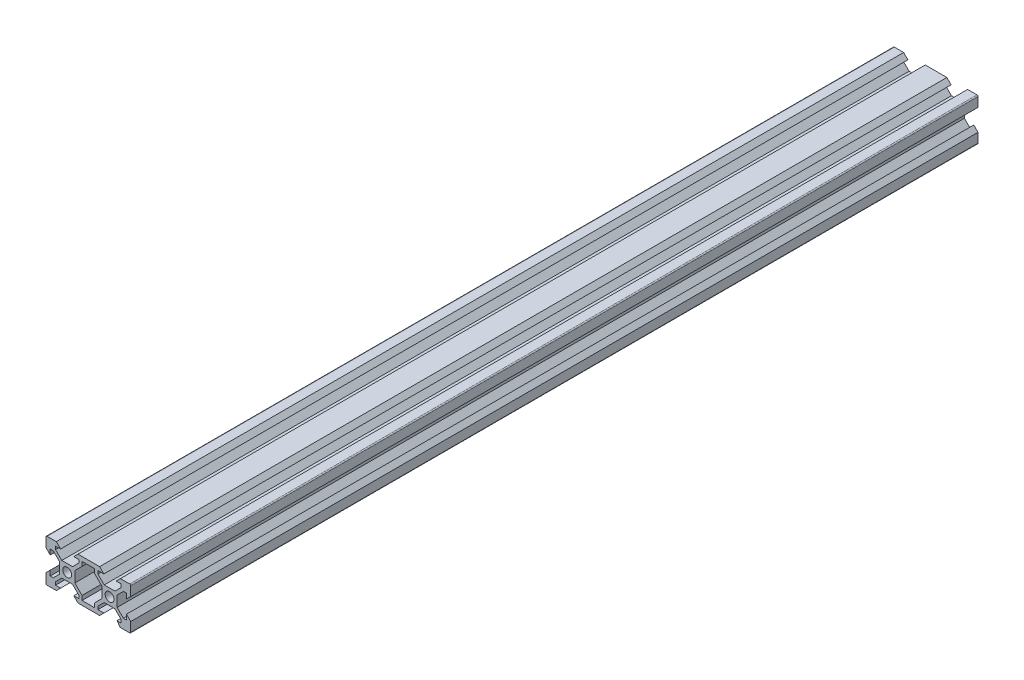
SolidWorks part; units mm, degrees
material "6063-T5"
ref_plane "Front Plane" through (0, 0, 0) normal (0, 0, 1) x (1, 0, 0)
ref_plane "Top Plane" through (0, 0, 0) normal (0, 1, 0) x (1, 0, 0)
ref_plane "Right Plane" through (0, 0, 0) normal (1, 0, 0) x (0, 0, -1)
sketch "Sketch1" plane through (0, 0, 0) normal (0, 0, 1) x (1, 0, 0)
  line L0 (-26.1395, 0) -> (11.0607, 0) construction
  line L1 (0, -20.0817) -> (0, 17.1243) construction
  line L2 (-20, 10.7318) -> (-20, -11.6858) construction
  line L3 (20, 11.8444) -> (20, -11.2237) construction
  line L4 (-23.1467, 10) -> (24.2381, 10) construction
  line L5 (23.8217, -10) -> (-26.7834, -10) construction
  line L6 (3, -5.9393) -> (3, -8)
  line L7 (-20, -10) -> (-15.5, -10)
  line L8 (-20, -10) -> (-20, -5.5)
  line L9 (-18, -5.5) -> (-16.5607, -5.5)
  line L10 (-15.5, -8) -> (-15.5, -6.5607)
  line L11 (-20, 10) -> (-15.5, 10)
  line L12 (-20, 10) -> (-20, 5.5)
  line L13 (-18, 5.5) -> (-16.5607, 5.5)
  line L14 (-15.5, 8) -> (-15.5, 6.5607)
  line L15 (20, 10) -> (15.5, 10)
  line L16 (20, 10) -> (20, 5.5)
  line L17 (18, 5.5) -> (16.5607, 5.5)
  line L18 (15.5, 8) -> (15.5, 6.5607)
  line L19 (20, -10) -> (15.5, -10)
  line L20 (20, -10) -> (20, -5.5)
  line L21 (18, -5.5) -> (16.5607, -5.5)
  line L22 (15.5, -8) -> (15.5, -6.5607)
  line L23 (4.5, -6.5607) -> (4.5, -8)
  line L24 (12.5393, 3.6) -> (15.5, 6.5607)
  line L25 (7.4607, -3.6) -> (4.5, -6.5607)
  line L27 (-4.5, 8) -> (-6.9, 8)
  line L28 (-12.5393, -3.6) -> (-15.5, -6.5607)
  line L29 (7.4607, 3.6) -> (4.5, 6.5607)
  line L30 (12.5393, -3.6) -> (15.5, -6.5607)
  line L31 (-13.6, -2.5393) -> (-16.5607, -5.5)
  line L32 (-13.6, 2.5393) -> (-16.5607, 5.5)
  line L33 (6.4, -2.5393) -> (3, -5.9393)
  line L34 (20, 5.5) -> (20, 5.1)
  line L35 (20, 5.1) -> (18, 3.1)
  line L36 (18, 3.1) -> (18, 5.5)
  line L37 (20, -5.5) -> (20, -5.1)
  line L38 (20, -5.1) -> (18, -3.1)
  line L39 (18, -3.1) -> (18, -5.5)
  line L40 (15.5, 10) -> (15.1, 10)
  line L41 (15.1, 10) -> (13.1, 8)
  line L42 (13.1, 8) -> (15.5, 8)
  line L43 (15.5, -10) -> (15.1, -10)
  line L44 (15.1, -10) -> (13.5138, -8)
  line L45 (13.5138, -8) -> (15.5, -8)
  line L46 (-15.5, 10) -> (-15.1, 10)
  line L47 (-15.1, 10) -> (-13.1, 8)
  line L48 (-13.1, 8) -> (-15.5, 8)
  line L49 (-20, 5.5) -> (-20, 5.1)
  line L50 (-20, 5.1) -> (-18, 3.1)
  line L51 (-18, 3.1) -> (-18, 5.5)
  line L52 (-20, -5.5) -> (-20, -5.1)
  line L53 (-20, -5.1) -> (-18, -3.1)
  line L54 (-18, -3.1) -> (-18, -5.5)
  line L55 (-15.5, -10) -> (-15.1, -10)
  line L56 (-15.1, -10) -> (-13.1, -8)
  line L57 (-13.1, -8) -> (-15.5, -8)
  line L58 (6.4, 2.5393) -> (3, 5.9393)
  line L59 (3, 8) -> (-3, 8)
  line L61 (-3, 5.9393) -> (-3, 8)
  line L62 (-12.5393, 3.6) -> (-15.5, 6.5607)
  line L63 (-4.5, 6.5607) -> (-4.5, 8)
  line L64 (4.5, 6.5607) -> (4.5, 8)
  line L65 (3, 5.9393) -> (3, 8)
  line L66 (13.6, 2.5393) -> (16.5607, 5.5)
  line L67 (12.1, 0) -> (30.0509, 0) construction
  line L68 (-7.4607, 3.6) -> (-4.5, 6.5607)
  line L69 (3, -8) -> (-3, -8)
  line L70 (-6.4, 2.5393) -> (-3, 5.9393)
  line L71 (13.6, -2.5393) -> (16.5607, -5.5)
  line L73 (-3, -5.9393) -> (-3, -8)
  line L74 (-4.5, -6.5607) -> (-4.5, -8)
  line L75 (-7.4607, -3.6) -> (-4.5, -6.5607)
  line L76 (-6.4, -2.5393) -> (-3, -5.9393)
  line L77 (5.3138, -10) -> (7.3138, -8)
  line L78 (7.3138, -8) -> (4.5, -8)
  line L79 (-6.9, -8) -> (-4.9, -10)
  line L80 (-4.9, -10) -> (5.3138, -10)
  line L81 (5.3138, 10) -> (7.3138, 8)
  line L82 (-4.9, 10) -> (5.3138, 10)
  line L83 (-6.9, 8) -> (-4.9, 10)
  line L84 (7.3138, 8) -> (4.5, 8)
  line L85 (7.4607, -3.6) -> (12.5393, -3.6)
  line L86 (-7.4607, -3.6) -> (-12.5393, -3.6)
  line L87 (-6.4, -2.5393) -> (-6.4, 2.5393)
  line L88 (-7.4607, 3.6) -> (-12.5393, 3.6)
  line L89 (-13.6, -2.5393) -> (-13.6, 2.5393)
  line L90 (6.4, -2.5393) -> (6.4, 2.5393)
  line L91 (13.6, -2.5393) -> (13.6, 2.5393)
  line L92 (7.4607, 3.6) -> (12.5393, 3.6)
  line L93 (-4.5, -8) -> (-6.9, -8)
  circle A0 centre (-10, 0) radius 2.1
  circle A1 centre (10, 0) radius 2.1
  dimension "D2" = 4.2
  dimension "D5" = 45
  dimension "D6" = 45
  dimension "D7" = 6.2
  dimension "D8" = 6.2
  dimension "D11" = 3.6
  dimension "D12" = 3.6
  dimension "D38" = 2.4
  dimension "D39" = 45
  dimension "D40" = 2.4
  dimension "D41" = 45
  dimension "D42" = 2
  dimension "D43" = 45
  dimension "D44" = 2.4
  dimension "D45" = 2
  dimension "D49" = 11
extrude "Boss-Extrude1" add sketch "Sketch1" along normal blind 400
fillet "Fillet1" radius 0.5 4 edges at (-20, -10, 200) (-20, 10, 200) (20, -10, 200) (20, 10, 200)
